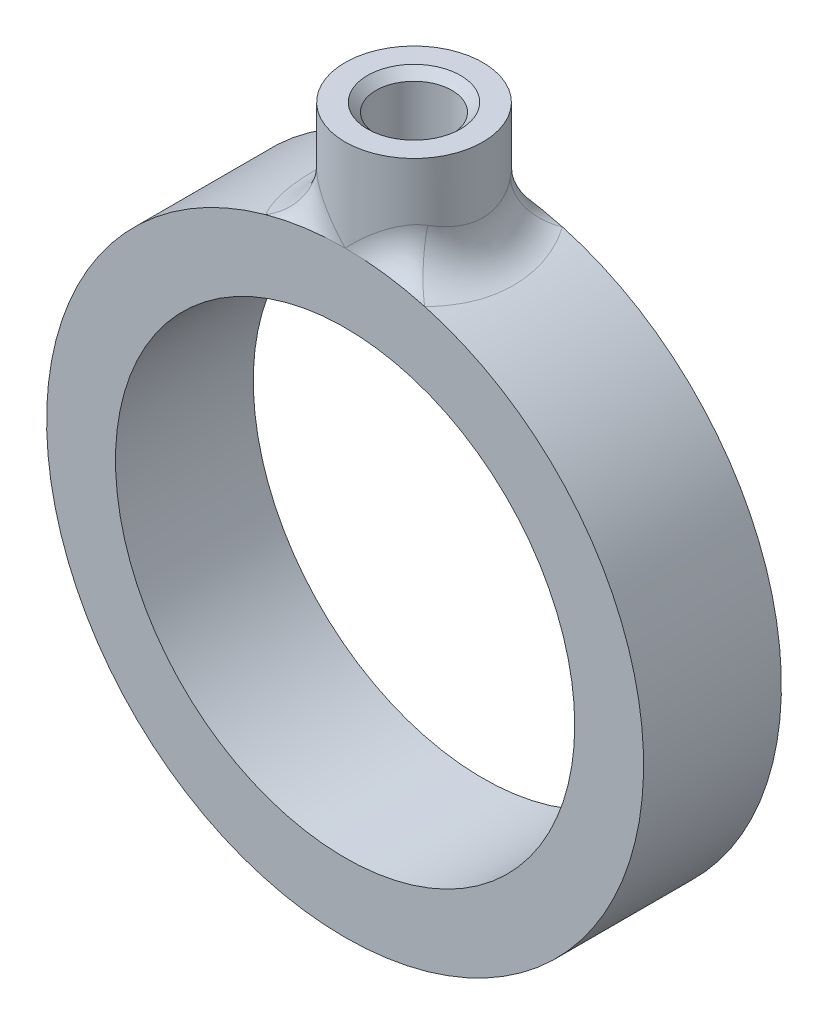
SolidWorks part; units mm, degrees
ref_plane "Front Plane" through (0, 0, 0) normal (0, 0, 1) x (1, 0, 0)
ref_plane "Top Plane" through (0, 0, 0) normal (0, 1, 0) x (1, 0, 0)
ref_plane "Right Plane" through (0, 0, 0) normal (1, 0, 0) x (0, 0, -1)
sketch "Sketch1" plane through (0, 0, 0) normal (0, 0, 1) x (1, 0, 0)
  circle A0 centre (0, 0) radius 13
  circle A1 centre (0, 0) radius 10
  dimension "D1" = 26
  dimension "D2" = 20
extrude "Boss-Extrude1" add sketch "Sketch1" along normal mid plane 6
sketch "Sketch2" plane through (0, 0, 0) normal (0, 1, 0) x (1, 0, 0)
  circle A0 centre (0, 0) radius 3
  dimension "D1" = 6
extrude "Boss-Extrude2" add sketch "Sketch2" against normal up to next from offset 17
fillet "Fillet1" radius 2 2 edges at (2.9196, 12.6679, 0.69) (-2.9196, 12.6679, 0.69)
hole_wizard "M4 Tapped Hole1" positions "Sketch3" profile "Sketch4" tap size "M4" standard "ISO"
sketch "Sketch3" plane through (0, 17, 0) normal (0, 1, 0) x (1, 0, 0)
  point P0 (0, 0)
sketch "Sketch4" plane through (0, 17, 0) normal (1, 0, 0) x (0, 0, 1)
  line L0 (0, 0) -> (0, 13.7914)
  line L1 (0, 13.7914) -> (1.65, 12.8)
  line L2 (1.65, 12.8) -> (1.65, 0.375)
  line L3 (1.65, 0.375) -> (2.025, 0)
  line L5 (2.025, 0) -> (0, 0)
  line L6 (-1.65, 0.375) -> (-2.025, 0) construction
  line L10 (0, 13.7914) -> (-1.65, 12.8) construction
  line L11 (0, -6.35) -> (0, 107.95) construction
  dimension "Tap Drill Dia." = 3.3
  dimension "Tap Drill Depth" = 12.8
  dimension "Near C'Sink Dia." = 4.05
  dimension "Near C'Sink Angle" = 90
  dimension "Drill Angle" = 118
cosmetic thread "Hole Thread1" parameters "D1"=7.1371, "D2"=4
